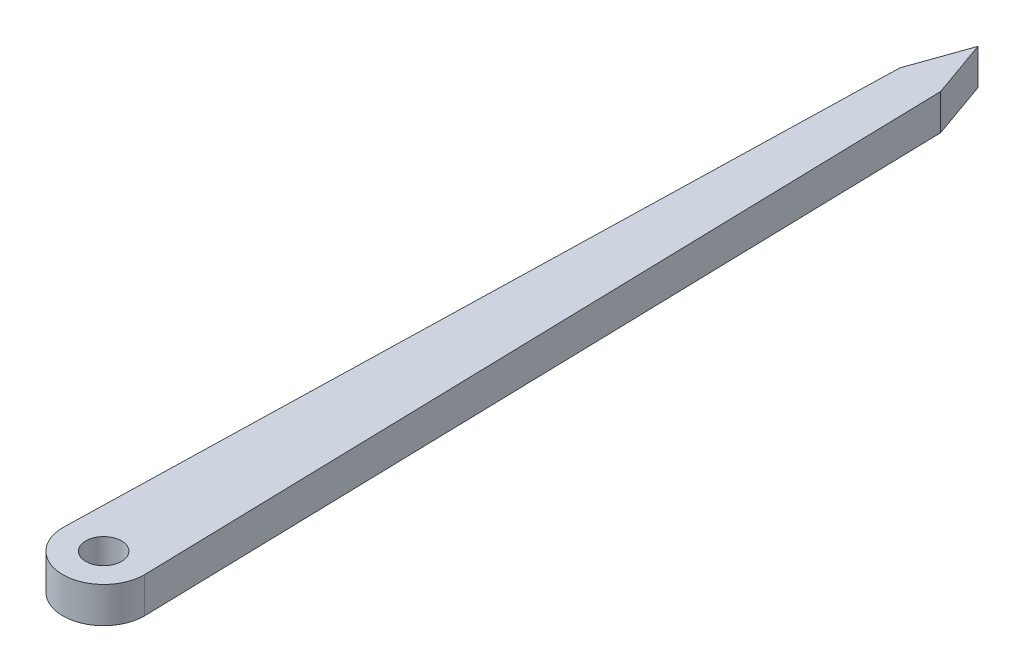
SolidWorks part; units mm, degrees
ref_plane "Přední rovina" through (0, 0, 0) normal (0, 0, 1) x (1, 0, 0)
ref_plane "Horní rovina" through (0, 0, 0) normal (0, 1, 0) x (1, 0, 0)
ref_plane "Pravá rovina" through (0, 0, 0) normal (1, 0, 0) x (0, 0, -1)
sketch "Skica1" plane through (0, 0, 0) normal (0, 1, 0) x (1, 0, 0)
  line L0 (-4, 0) -> (-2, 80)
  line L1 (-2, 80) -> (0, 85.6569)
  line L2 (0, 85.6569) -> (2, 80)
  line L3 (2, 80) -> (4, 0)
  circle A4 centre (0, 0) radius 4
  circle A5 centre (0, 0) radius 1.75
  point P2 (0, 0)
  dimension "D1" = 8
  dimension "D2" = 3.5
  dimension "D7" = 4
  dimension "D8" = 80
  dimension "D3" = 0
  dimension "D4" = 6
  dimension "D5" = 6
  dimension "D6" = 80
extrude "Přidat vysunutím1" add sketch "Skica1" along normal blind 3.5 contours A4 L3 L2 L1 L0 | L3 A4 L0 A5 region at (-3.8844, 0, -0.0971) region at (0, 0, -38.5053)
